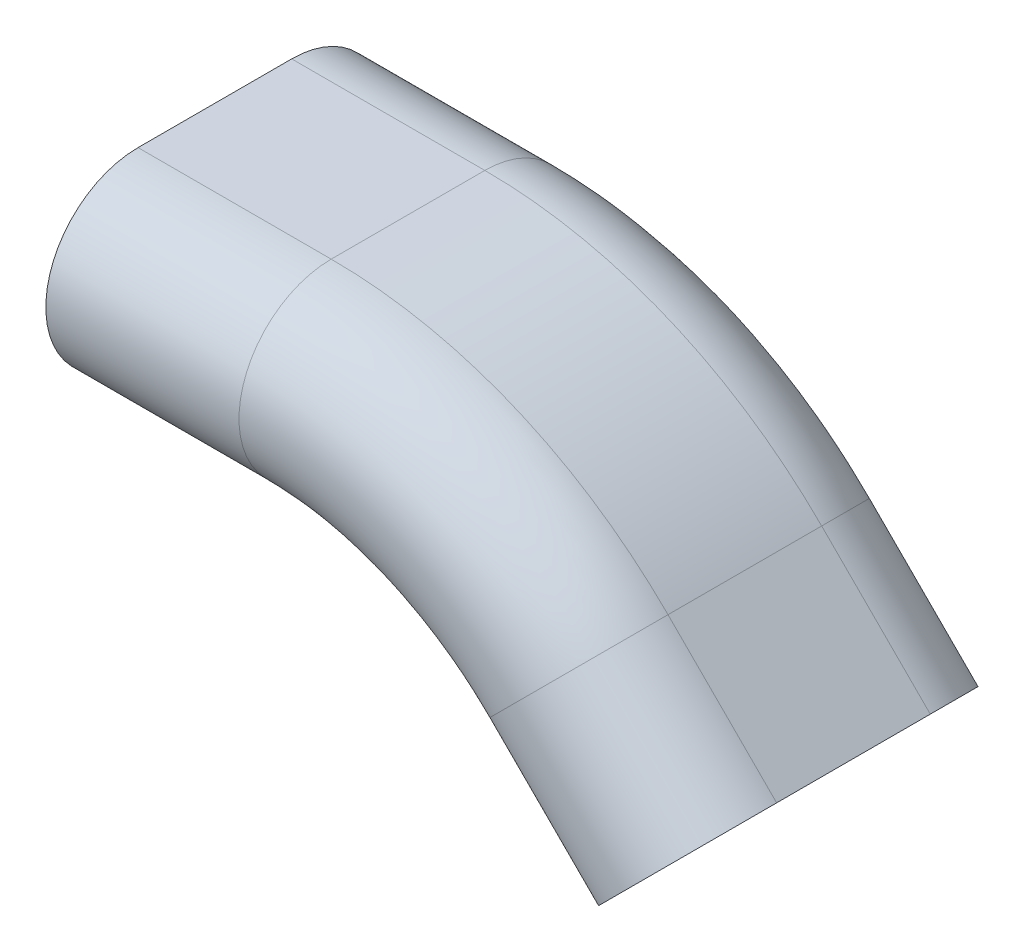
SolidWorks part; units mm, degrees
ref_plane "Front" through (0, 0, 0) normal (0, 0, 1) x (1, 0, 0)
ref_plane "Top" through (0, 0, 0) normal (0, 1, 0) x (1, 0, 0)
ref_plane "Right" through (0, 0, 0) normal (1, 0, 0) x (0, 0, -1)
sketch "Sketch2path" plane through (0, 0, 0) normal (0, 0, 1) x (1, 0, 0)
  line L0 (30.2496, -7.3223) -> (37.3206, -14.3934)
  line L1 (0, 0) -> (12.5719, 0)
  arc A1 (12.5719, 0) -> (30.2496, -7.3223) centre (12.5719, -25) cw
  point P5 (22.9272, 0)
  dimension "D1" = 40
  dimension "D2" = 45
  dimension "D4" = 25
  dimension "D3" = 10
sketch "Sketch3" plane through (0, 0, 0) normal (1, 0, 0) x (0, 0, -1)
  line L6 (0, 91.8161) -> (0, -91.8161) construction
  line L7 (-5, 0) -> (5, 0) construction
  line L8 (-5, 5) -> (5, 5)
  line L9 (-5, -5) -> (5, -5)
  line L10 (-5, 6) -> (5, 6)
  line L11 (-5, -6) -> (5, -6)
  arc A6 (5, -6) -> (5, 6) centre (5, 0) ccw
  arc A7 (-5, 5) -> (-5, -5) centre (-5, 0) ccw
  arc A8 (5, -5) -> (5, 5) centre (5, 0) ccw
  arc A9 (-5, 6) -> (-5, -6) centre (-5, 0) ccw
  point P26 (0, 0)
  dimension "D1" = 6
  dimension "D2" = 5
sweep "Sweep1" add profiles "Sketch3" path "Sketch2path"
ref_point "Point1S1"
ref_point "Point2S3"
ref_axis "os podluzna S1" through (0, 0, 0) along (1, 0, 0)
ref_axis "os podluzna S3" through (37.3206, -14.3934, 0) along (0.7071, -0.7071, 0)
ref_plane "Plane4 polowki" through (0, 0, 0) normal (0, 0, 1) x (1, 0, 0)
fillet "Fillet1" radius 0.5 4 edges at (0, 0, 10) (0, 5, 0) (0, 0, -10) (0, -5, 0)
sketch "Sketch13" plane through (0, 0, 0) normal (0, 1, 0) x (1, 0, 0)
  line L1 (15.99, -6) -> (16.01, -6)
  line L2 (14, -7.99) -> (14, -10)
  line L3 (14, -10) -> (18, -10)
  line L4 (18, -7.99) -> (18, -10)
  arc A0 (18, -7.99) -> (16.01, -6) centre (16.01, -7.99) ccw
  arc A1 (15.99, -6) -> (14, -7.99) centre (15.99, -7.99) ccw
  point P8 (18, -6)
  point P11 (14, -6)
  dimension "D4" = 6
  dimension "D1" = 1.99
  dimension "D2" = 14
  dimension "D3" = 18
  dimension "D5" = 10
extrude "Boss-Extrude6" add sketch "Sketch13" along normal up to next and the other way up to next
ref_plane "Plane2" through (6.286, 0, 0) normal (1, 0, 0) x (0, 0, -1)
mirror "Mirror1" about plane through (6.286, 0, 0) normal (1, 0, 0) rebuild error yes
mirror "Mirror2" about plane through (0, 0, 0) normal (0, 0, 1) rebuild error yes
